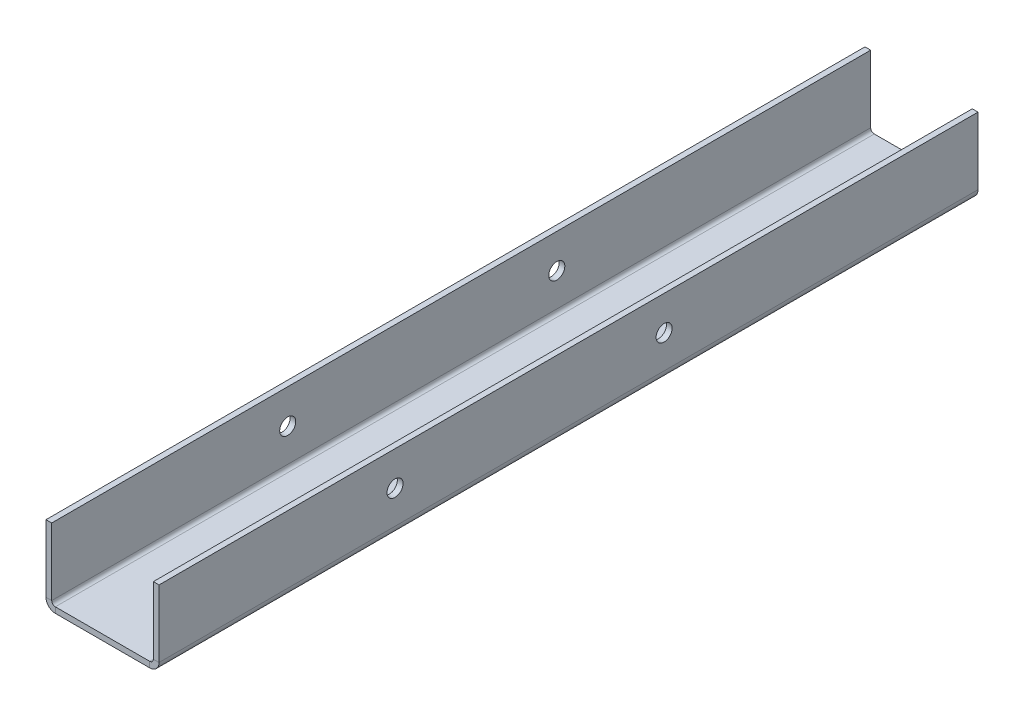
SolidWorks part; units mm, degrees
note: The reader was unsure of these and kept them because the rebuilt part matched: flange length of "Edge-Flange1", "Edge-Flange2".
ref_plane "Front Plane" through (0, 0, 0) normal (0, 0, 1) x (1, 0, 0)
ref_plane "Top Plane" through (0, 0, 0) normal (0, 1, 0) x (1, 0, 0)
ref_plane "Right Plane" through (0, 0, 0) normal (1, 0, 0) x (0, 0, -1)
sketch "Sketch1" plane through (0, 0, 0) normal (0, 1, 0) x (1, 0, 0)
  line L1 (10, -86.75) -> (-10, -86.75)
  line L2 (10, -86.75) -> (10, 86.75)
  line L3 (10, 86.75) -> (-10, 86.75)
  line L4 (-10, -86.75) -> (-10, 86.75)
  line L5 (10, -86.75) -> (-10, 86.75) construction
  line L6 (10, 86.75) -> (-10, -86.75) construction
  point P0 (0, 0)
  dimension "D1" = 173.5
  dimension "D2" = 20
base flange "Base-Flange1" sketch "Sketch1" thickness 1.21 reverse thickness direction no parameters "D1"=0.762
edge flange "Edge-Flange1" sketch "Sketch8" flange angle 90 flange length 15 flange position bend outside bend radius 0.762 thickness 1.21 relief rectangular parameters "D6"=10
sketch "Sketch8" plane through (-10, 0, 0) normal (-1, 0, 0) x (0, 0, 1)
  line L0 (-86.75, 0) -> (86.75, 0) construction
  line L1 (-86.75, 0) -> (86.75, 0)
  line L2 (-86.75, 0) -> (-86.75, 15)
  line L3 (-86.75, 15) -> (86.75, 15)
  line L4 (86.75, 15) -> (86.75, 0)
bend "EdgeBend1" bend radius 0.762 bend angle 90 parameters "D5"=1
edge flange "Edge-Flange2" sketch "Sketch11" flange angle 90 flange length 15 flange position bend outside bend radius 0.762 thickness 1.21 relief rectangular parameters "D6"=10
sketch "Sketch11" plane through (10, 0, 0) normal (1, 0, 0) x (0, 0, -1)
  line L0 (-86.75, 0) -> (86.75, 0) construction
  line L1 (-86.75, 0) -> (86.75, 0)
  line L2 (-86.75, 0) -> (-86.75, 15)
  line L3 (-86.75, 15) -> (86.75, 15)
  line L4 (86.75, 15) -> (86.75, 0)
bend "EdgeBend2" bend radius 0.762 bend angle 90 parameters "D5"=2
sketch "Sketch14" plane through (0, -1.21, 0) normal (0, -1, 0) x (-1, 0, 0)
  circle A0 centre (0, -69.75) radius 1.2
  dimension "D1" = 0
extrude "Cut-Extrude1" cut sketch "Sketch14" against normal blind 5 contours A0 normal cut yes
hole_wizard "M3 Clearance Hole1" positions "Sketch15" profile "Sketch16" hole size "M3" standard "ANSI Metric" end condition through all
sketch "Sketch15" plane through (-11.972, 85.7016, 15.2023) normal (-1, 0, 0) x (0, 0, -1)
  line L0 (35.4523, 77.9396) -> (-21.5477, 77.9396)
  point P0 (-21.5477, 77.9396)
  point P1 (35.4523, 77.9396)
sketch "Sketch16" plane through (-11.972, 7.762, 36.75) normal (0, 1, 0) x (0, 0, 1)
  line L0 (0, 0) -> (0, 23.944)
  line L1 (0, 23.944) -> (1.7, 23.944)
  line L2 (1.7, 23.944) -> (1.7, 0)
  line L5 (1.7, 0) -> (0, 0)
  line L11 (0, -6.35) -> (0, 107.95) construction
  dimension "Thru Hole Dia." = 3.4
  dimension "Thru Hole Depth" = 23.944
sketch "Bend-Lines1" plane through (0, 0, 0) normal (0, 1, 0) x (1, 0, 0)
sketch "Bounding-Box1" plane through (0, 0, 0) normal (0, 1, 0) x (1, 0, 0)
sheet metal parameters "Sheet-Metal(1)" thickness 1.21 parameters "D1"=0.762
flat pattern "Flat-Pattern(1)" [suppressed]
sketch "Bend-Lines2" plane through (0, 0, 0) normal (0, 1, 0) x (1, 0, 0)
sketch "Bounding-Box2" [suppressed] plane through (0, 0, 0) normal (0, 1, 0) x (1, 0, 0)
sheet metal parameters "Sheet-Metal(2)" thickness 1.21 parameters "D1"=0.762
flat pattern "Flat-Pattern(1)" [suppressed]
sketch "Bend-Lines2" plane through (0, 0, 0) normal (0, 1, 0) x (1, 0, 0)
sketch "Bounding-Box2" [suppressed] plane through (0, 0, 0) normal (0, 1, 0) x (1, 0, 0)
bend of the flat pattern "Flatten-<EdgeBend1>1"
sheet metal parameters "Sheet-Metal(3)" thickness 1.21 parameters "D1"=0.762
flat pattern "Flat-Pattern(1)" [suppressed]
sketch "Bend-Lines2" plane through (0, 0, 0) normal (0, 1, 0) x (1, 0, 0)
sketch "Bounding-Box2" [suppressed] plane through (0, 0, 0) normal (0, 1, 0) x (1, 0, 0)
bend of the flat pattern "Flatten-<EdgeBend1>1"
bend of the flat pattern "Flatten-<EdgeBend2>1"
sheet metal parameters "Sheet-Metal(4)" thickness 1.21 parameters "D1"=0.762
flat pattern "Flat-Pattern(1)" [suppressed]
sketch "Bend-Lines2" plane through (0, 0, 0) normal (0, 1, 0) x (1, 0, 0)
sketch "Bounding-Box2" [suppressed] plane through (0, 0, 0) normal (0, 1, 0) x (1, 0, 0)
bend of the flat pattern "Flatten-<EdgeBend1>1"
bend of the flat pattern "Flatten-<EdgeBend2>1"
sheet metal parameters "Sheet-Metal(5)" thickness 1.21 parameters "D1"=0.762
flat pattern "Flat-Pattern(1)" [suppressed]
sketch "Bend-Lines2" plane through (0, 0, 0) normal (0, 1, 0) x (1, 0, 0)
sketch "Bounding-Box2" [suppressed] plane through (0, 0, 0) normal (0, 1, 0) x (1, 0, 0)
bend of the flat pattern "Flatten-<EdgeBend1>1"
bend of the flat pattern "Flatten-<EdgeBend2>1"
